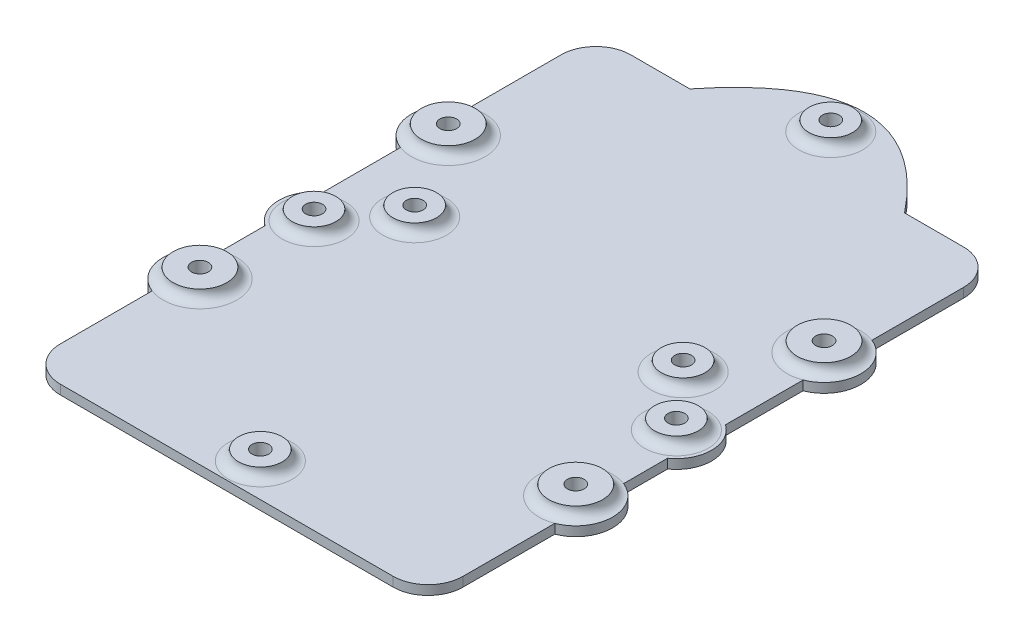
SolidWorks part; units mm, degrees
ref_plane "Front Plane" through (0, 0, 0) normal (0, 0, 1) x (1, 0, 0)
ref_plane "Top Plane" through (0, 0, 0) normal (0, 1, 0) x (1, 0, 0)
ref_plane "Right Plane" through (0, 0, 0) normal (1, 0, 0) x (0, 0, -1)
sketch "Sketch1"
sketch "Sketch2" plane through (0, 0, 0) normal (0, 1, 0) x (1, 0, 0)
  line L1 (-5.0794, 83.4958) -> (54.9206, 83.4958)
  line L2 (-5.0794, 83.4958) -> (-5.0794, -1.5042)
  line L3 (-5.0794, -1.5042) -> (54.9206, -1.5042)
  line L4 (54.9206, 83.4958) -> (54.9206, -1.5042)
  dimension "D1" = 60
  dimension "D2" = 85
extrude "Boss-Extrude1" add sketch "Sketch2" against normal blind 1.4
sketch "Sketch13" plane through (0, 0, 0) normal (0, 1, 0) x (1, 0, 0)
  line L0 (54.9206, 83.4958) -> (-5.0794, 83.4958) construction
  line L1 (54.9206, -1.5042) -> (54.9206, 83.4958) construction
  line L2 (-5.0794, 83.4958) -> (-5.0794, -1.5042) construction
  line L3 (54.9206, 83.4958) -> (-5.0794, 83.4958)
  line L5 (54.9206, -1.5042) -> (54.9206, 83.4958) construction
  line L7 (54.9206, -1.5042) -> (54.9206, 83.4958)
  line L8 (-5.0794, 83.4958) -> (-5.0794, -1.5042) construction
  line L9 (-5.0794, 83.4958) -> (-5.0794, -1.5042)
  circle A0 centre (51.9206, 38.4958) radius 1.25
  circle A1 centre (-2.0794, 38.4958) radius 1.25
  circle A2 centre (24.9206, 88.4958) radius 1.25
  circle A3 centre (51.9206, 38.4958) radius 3.25
  circle A4 centre (-2.0794, 38.4958) radius 3.25
  circle A5 centre (24.9206, 88.4958) radius 3.25
  circle A6 centre (51.9206, 38.4958) radius 5.25
  circle A7 centre (-2.0794, 38.4958) radius 5.25
  spline S0 degree 2 poles (40.9206, 83.4958) (24.9206, 103.4958) (8.9206, 83.4958) knots 0 0 0 1 1 1
  point P8 (24.9206, 83.4958)
  line M14 (-5.0794, 83.4958) -> (-5.0794, -1.5042)
  line M16 (54.9206, -1.5042) -> (54.9206, 83.4958)
  dimension "D1" = 2.5
  dimension "D2" = 2.5
  dimension "D3" = 2.5
  dimension "D4" = 5
  dimension "D5" = 3
  dimension "D6" = 3
  dimension "D7" = 45
  dimension "D8" = 14
  dimension "D9" = 14
  dimension "D10" = 10
  dimension "D11" = 2
  dimension "D12" = 2
extrude "Cut-Extrude7" cut sketch "Sketch13" against normal blind 2 contours A6 | A7
extrude "Boss-Extrude6" add sketch "Sketch13<4>" along normal blind 1.5 separate body contours A3 A0 | A4 A1 | A5 A2 | A3 | A4 region at (55.021, 0, -38.4958) region at (54.8305, 0, -38.4958) region at (-1.4597, 0, -41.5943) region at (-5.1797, 0, -38.4958) region at (21.7626, 0, -88.4958)
sketch "Sketch13<4>" plane through (0, 0, 0) normal (0, 1, 0) x (1, 0, 0) same geometry as "Sketch13"
extrude "Boss-Extrude18" add sketch "Sketch13<14>" against normal blind 1.4 contours A6 | A7
sketch "Sketch13<14>" plane through (0, 0, 0) normal (0, 1, 0) x (1, 0, 0) same geometry as "Sketch13"
extrude "Boss-Extrude19" add sketch "Sketch13<17>" against normal blind 1.4 contours L3 S0 A5 | A5 A2 region at (24.9206, 0, -83.8311) region at (21.7626, 0, -88.4958)
sketch "Sketch13<17>" plane through (0, 0, 0) normal (0, 1, 0) x (1, 0, 0) same geometry as "Sketch13"
extrude "Cut-Extrude8" cut sketch "Sketch13<15>" against normal through all contours A0 | A1 region at (51.9206, 0, -38.4958)
sketch "Sketch13<15>" plane through (0, 0, 0) normal (0, 1, 0) x (1, 0, 0) same geometry as "Sketch13"
fillet "Fillet9" radius 1.5 3 edges at (-2.0794, 0, -35.2458) (51.9206, 0, -35.2458) (24.9206, 0, -85.2458)
sketch "Sketch11" plane through (0, 0, 0) normal (0, 1, 0) x (1, 0, 0)
  line L0 (-5.0794, -1.5042) -> (54.9206, -1.5042) construction
  line L3 (54.9206, 42.8042) -> (54.9206, 83.4958) construction
  line L4 (-5.0794, 83.4958) -> (-5.0794, 42.8042) construction
  circle A0 centre (24.9206, 3.4958) radius 1.25
  circle A1 centre (44.9206, 46.4958) radius 1.25
  circle A2 centre (4.9206, 46.4958) radius 1.25
  circle A3 centre (24.9206, 3.4958) radius 3.25
  circle A4 centre (44.9206, 46.4958) radius 3.25
  circle A5 centre (4.9206, 46.4958) radius 3.25
  point P8 (24.9206, -1.5042)
  dimension "D1" = 2.5
  dimension "D2" = 2.5
  dimension "D3" = 2.5
  dimension "D4" = 10
  dimension "D5" = 10
  dimension "D6" = 48
  dimension "D7" = 5
  dimension "D8" = 2
extrude "Boss-Extrude5" add sketch "Sketch11" along normal blind 1.5 contours A3 A0 | A5 A2 | A4 A1 region at (21.7626, 0, -3.4958) region at (41.7626, 0, -46.4958) region at (1.7626, 0, -46.4958)
fillet "Fillet1" radius 5.2 4 edges at (-5.0794, -0.7, 1.5042) (54.9206, -0.7, 1.5042) (54.9206, -0.7, -83.4958) (-5.0794, -0.7, -83.4958)
sketch "Sketch10" plane through (0, 0, 0) normal (0, 1, 0) x (1, 0, 0)
  line L0 (23.4754, 64.1747) -> (23.4754, 17.0271) construction
  text T0 "this side down" font "Century Gothic" height in points 14
extrude "Boss-Extrude4" [suppressed] add sketch "Sketch10" along normal blind 1
extrude "Cut-Extrude3" cut sketch "Sketch11<3>" against normal through all contours A0 | A1 | A2 region at (24.9206, 0, -3.4958) region at (44.9206, 0, -46.4958) region at (4.9206, 0, -46.4958)
sketch "Sketch11<3>" plane through (0, 0, 0) normal (0, 1, 0) x (1, 0, 0) same geometry as "Sketch11"
fillet "Fillet4" radius 1.5 3 edges at (4.9206, 0, -43.2458) (44.9206, 0, -43.2458) (24.9206, 0, -0.2458)
extrude "Boss-Extrude11" add sketch "Sketch13<6>" against normal blind 1.4 contours A4 A1 M14 | A3 A0 M16 region at (54.8305, 0, -38.4958) region at (-1.4597, 0, -41.5943)
sketch "Sketch13<6>" plane through (0, 0, 0) normal (0, 1, 0) x (1, 0, 0) same geometry as "Sketch13"
sketch "Sketch3" plane through (0, 0, 0) normal (0, 1, 0) x (1, 0, 0)
  line L0 (-5.0794, 83.4958) -> (-5.0794, -1.5042) construction
  line L1 (54.9206, -1.5042) -> (54.9206, 83.4958) construction
  line L2 (54.9206, 83.4958) -> (-5.0794, 83.4958) construction
  line L3 (0.1206, -1.5042) -> (49.7206, -1.5042) construction
  line L4 (54.9206, -1.5042) -> (54.9206, 83.4958)
  line L5 (-5.0794, 83.4958) -> (-5.0794, -1.5042)
  line L6 (52.9206, 59.4958) -> (58.4206, 59.4958) construction
  line L7 (52.9206, 22.4958) -> (58.4206, 22.4958) construction
  line L8 (-3.0794, 22.4958) -> (-8.5794, 22.4958) construction
  line L9 (-3.0794, 59.4958) -> (-8.5794, 59.4958) construction
  circle A0 centre (52.9206, 22.4958) radius 4
  circle A1 centre (-3.0794, 22.4958) radius 4
  circle A2 centre (52.9206, 59.4958) radius 4
  circle A3 centre (-3.0794, 59.4958) radius 4
  circle A4 centre (52.9206, 59.4958) radius 1.25
  circle A5 centre (52.9206, 22.4958) radius 1.25
  circle A6 centre (-3.0794, 59.4958) radius 1.25
  circle A7 centre (-3.0794, 22.4958) radius 1.25
  circle A8 centre (52.9206, 59.4958) radius 5.5
  circle A9 centre (52.9206, 22.4958) radius 5.5
  circle A10 centre (-3.0794, 59.4958) radius 5.5
  circle A11 centre (-3.0794, 22.4958) radius 5.5
  dimension "D2" = 8
  dimension "D3" = 8
  dimension "D4" = 8
  dimension "D5" = 2.5
  dimension "D6" = 2.5
  dimension "D7" = 2.5
  dimension "D8" = 2.5
  dimension "D13" = 11
  dimension "D14" = 11
  dimension "D15" = 11
  dimension "D16" = 11
  dimension "D17" = 8
  dimension "D9" = 2
  dimension "D10" = 2
  dimension "D11" = 24
  dimension "D12" = 24
sketch "Sketch14"
extrude "Boss-Extrude9" add sketch "Sketch3" against normal blind 1.4 contours L4 A9 A0 | L4 A0 | L4 A2 | L4 A8 A2 | L5 A1 | L5 A11 A1 | L5 A3 | L5 A10 A3 region at (55.0289, 0, -55.202) region at (55.0289, 0, -18.202) region at (55.7407, 0, -22.4958) region at (55.7407, 0, -59.4958) region at (-5.1876, 0, -26.7896) region at (-5.1876, 0, -63.7896) region at (-5.8994, 0, -59.4958) region at (-5.8994, 0, -22.4958)
extrude "Boss-Extrude10" add sketch "Sketch3<9>" along normal blind 1.5 contours L4 A0 A5 | L4 A0 | L5 A1 A7 | L5 A1 | L5 A3 A6 | L5 A3 | L4 A2 | L4 A2 A4 region at (49.0206, 0, -22.4958) region at (55.7407, 0, -22.4958) region at (49.0206, 0, -59.4958) region at (55.7407, 0, -59.4958) region at (-1.1294, 0, -62.8733) region at (-5.8994, 0, -59.4958) region at (-1.1294, 0, -25.8733) region at (-5.8994, 0, -22.4958)
sketch "Sketch3<9>" plane through (0, 0, 0) normal (0, 1, 0) x (1, 0, 0) same geometry as "Sketch3"
extrude "Cut-Extrude6" cut sketch "Sketch3<10>" against normal through all contours A5 | A7 | A4 | A6 region at (52.9206, 0, -59.4958) region at (52.9206, 0, -22.4958) region at (-3.0794, 0, -59.4958) region at (-3.0794, 0, -22.4958)
sketch "Sketch3<10>" plane through (0, 0, 0) normal (0, 1, 0) x (1, 0, 0) same geometry as "Sketch3"
fillet "Fillet6" radius 1.5 4 edges at (52.9206, 0, -55.4958) (-3.0794, 0, -55.4958) (-3.0794, 0, -18.4958) (52.9206, 0, -18.4958)
